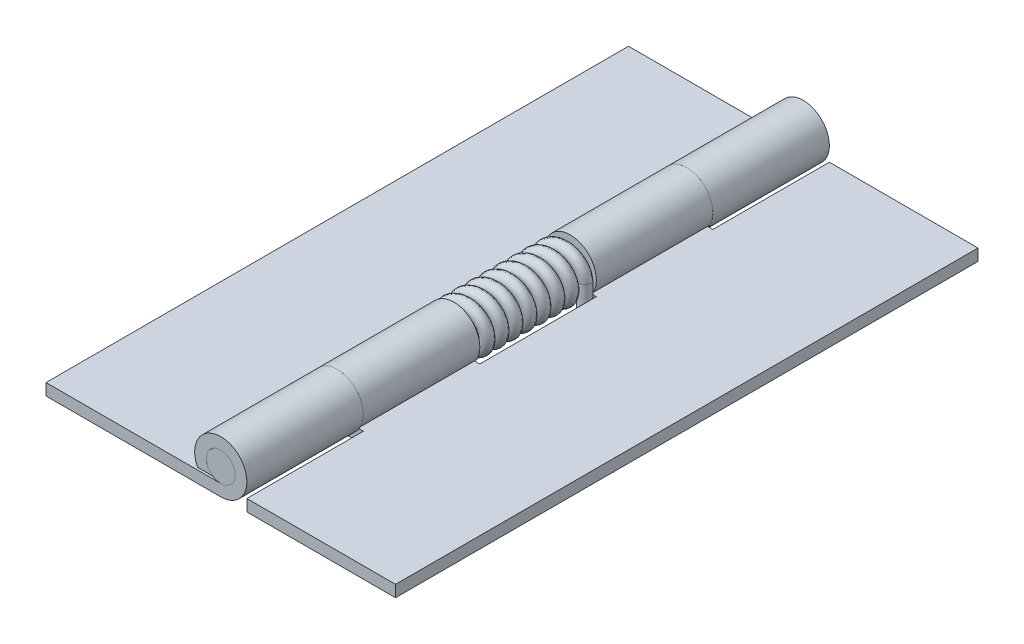
SolidWorks part; units mm, degrees
ref_plane "Front" through (0, 0, 0) normal (0, 0, 1) x (1, 0, 0)
ref_plane "Top" through (0, 0, 0) normal (0, 1, 0) x (1, 0, 0)
ref_plane "Right" through (0, 0, 0) normal (1, 0, 0) x (0, 0, -1)
sketch "Sketch1" plane through (0, 0, 0) normal (0, 0, 1) x (1, 0, 0)
  line L0 (-9.525, 0) -> (0, 0)
  line L1 (-9.525, 0) -> (-9.525, 0.635)
  line L2 (-9.525, 0.635) -> (0, 0.635)
  line L3 (-9.525, 0) -> (9.525, 0) construction
  line L4 (-1.2598, 0.762) -> (-0.4288, 0.762)
  circle A0 centre (0, 1.4224) radius 1.4224 construction
  circle A1 centre (0, 1.4224) radius 0.7874 construction
  arc A2 (0, 0.635) -> (-0.4288, 0.762) centre (0, 1.4224) ccw
  arc A3 (0, 0) -> (-1.2598, 0.762) centre (0, 1.4224) ccw
  dimension "D1" = 0.127
  dimension "Pin Dia" = 1.5748
  dimension "Thickness" = 0.635
  dimension "Open Wd" = 19.05
extrude "Extrude1" add sketch "Sketch1" against normal blind 31.75
sketch "Sketch2" plane through (0, 0, 0) normal (0, 1, 0) x (1, 0, 0)
  line L0 (1.4224, 0) -> (1.4224, 31.75) construction
  line L2 (-9.525, 0) -> (9.525, 0) construction
  line L5 (-1.4224, 31.75) -> (-1.4224, 0) construction
  line L6 (-1.4224, 25.4) -> (-1.4224, 31.75) construction
  line L11 (1.4224, 6.35) -> (-1.4224, 6.35)
  line L12 (1.4224, 6.35) -> (1.4224, 12.7)
  line L13 (1.4224, 12.7) -> (-1.4224, 12.7) construction
  line L14 (-1.4224, 6.35) -> (-1.4224, 12.7)
  line L16 (-1.4224, 6.35) -> (-1.4224, 0) construction
  line L17 (-1.4224, 12.7) -> (-1.4224, 19.05)
  line L19 (-1.4224, 19.05) -> (1.4224, 19.05) construction
  line L20 (-1.4224, 19.05) -> (-1.4224, 25.4)
  line L21 (-1.4224, 25.4) -> (1.4224, 25.4)
  line L22 (1.4224, 19.05) -> (1.4224, 25.4)
  line L23 (1.4224, 19.05) -> (1.4224, 12.7)
  dimension "D1" = 6.35
extrude "Cut-Extrude1" cut sketch "Sketch2" along normal through all
sketch "Sketch3" plane through (0, 0, 0) normal (0, 0, 1) x (1, 0, 0)
  line L0 (0, 0) -> (9.525, 0)
  line L1 (9.525, 0) -> (9.525, 0.635)
  line L2 (9.525, 0.635) -> (0, 0.635)
  line L3 (0.4288, 0.762) -> (1.2598, 0.762)
  line L4 (-1.2598, 0.762) -> (-0.4288, 0.762) construction
  arc A0 (0, 0) -> (1.2598, 0.762) centre (0, 1.4224) cw
  arc A1 (0, 0) -> (-1.2598, 0.762) centre (0, 1.4224) ccw construction
  arc A2 (0, 0.635) -> (0.4288, 0.762) centre (0, 1.4224) cw
  arc A3 (0, 0.635) -> (-0.4288, 0.762) centre (0, 1.4224) ccw construction
extrude "Extrude2" add sketch "Sketch3" against normal up to surface (31.75 mm away) separate body up to face at (-3.1558, 1.0886, -31.75)
sketch "Sketch4" plane through (0, 0, 0) normal (0, 1, 0) x (1, 0, 0)
  line L0 (-1.4224, 19.05) -> (-1.4224, 12.7)
  line L1 (-1.4224, 12.7) -> (1.4224, 12.7)
  line L2 (-1.4224, 0) -> (-1.4224, 6.35)
  line L3 (-1.4224, 6.35) -> (1.4224, 6.35)
  line L4 (1.4224, 6.35) -> (1.4224, 0)
  line L5 (1.4224, 0) -> (-1.4224, 0)
  line L7 (-1.4224, 19.05) -> (1.4224, 19.05)
  line L8 (1.4224, 12.7) -> (1.4224, 19.05)
  line L9 (-1.4224, 31.75) -> (1.4224, 31.75)
  line L10 (-1.4224, 31.75) -> (-1.4224, 25.4)
  line L11 (-1.4224, 25.4) -> (1.4224, 25.4)
  line L12 (1.4224, 31.75) -> (1.4224, 25.4)
extrude "Cut-Extrude2" cut sketch "Sketch4" along normal through all
sketch "Sketch5" plane through (0, 0, 0) normal (0, 0, 1) x (1, 0, 0)
  circle A0 centre (0, 1.4224) radius 0.7874
  arc A2 (0, 0.635) -> (-0.4288, 0.762) centre (0, 1.4224) ccw construction
extrude "Extrude3" add sketch "Sketch5" against normal up to surface (31.75 mm away) separate body up to face at (-3.1558, 1.0886, -31.75)
ref_plane "Plane4" through (0, 1.4224, 0) normal (0, 1, 0) x (-1, 0, 0)
sketch "Sketch15" plane through (0, 1.4224, 0) normal (0, 1, 0) x (0, 0, -1)
  line L0 (19.05, 1.4224) -> (19.05, -1.4224) construction
  line L2 (12.7, -1.4224) -> (12.7, 1.4224) construction
  line L3 (6.35, -1.4224) -> (12.7, -1.4224) construction
  line L4 (6.35, 1.4224) -> (12.7, 1.4224) construction
  circle A0 centre (18.7325, -1.1049) radius 0.3175
  circle A1 centre (13.0175, 1.1049) radius 0.3175
  dimension "D1" = 0.635
sketch "Sketch6" plane through (-38.1, 1.4224, -35.9283) normal (0, 1, 0) x (1, 0, 0)
  circle A0 centre (39.2049, -17.1958) radius 0.3175
  dimension "D1" = 0.635
ref_plane "Plane5" through (0, 0, -18.7325) normal (0, 0, 1) x (1, 0, 0)
sketch "Sketch9" plane through (0, 0, -18.7325) normal (0, 0, 1) x (1, 0, 0)
  line L2 (0, 1.4224) -> (1.1049, 1.4224) construction
  circle A0 centre (0, 1.4224) radius 1.1049
curve "Helix/Spiral2" pitch 0.762 height 5.715 radius 1.1049 centre (0, 1.4224, -18.7325) axis (0, 0, 1) start towards (1, 0, 0)
sketch "Sketch10" plane through (0, 0, -18.7325) normal (0, 0, 1) x (1, 0, 0)
  line L1 (1.5018, -0.3175) -> (8.3344, -0.3175)
  line L2 (1.4224, 0) -> (9.525, 0) construction
  line L3 (1.1049, 1.4224) -> (1.1049, 0.0794)
  line L5 (1.4224, 1.4224) -> (0.7874, 1.4224) construction
  arc A2 (1.1049, 0.0794) -> (1.5018, -0.3175) centre (1.5018, 0.0794) ccw
  dimension "D3" = 0.3969
  dimension "D1" = 0.3175
  dimension "D2" = 8.3344
sweep "Sweep12" add profiles "Sketch6" path "Helix/Spiral2"
sweep "Sweep5" add profiles "Sketch6<4>" path "Sketch10"
sketch "Sketch6<4>" plane through (-38.1, 1.4224, -35.9283) normal (0, 1, 0) x (1, 0, 0) same geometry as "Sketch6"
sketch "Sketch11" plane through (0, 1.4224, 0) normal (0, -1, 0) x (1, 0, 0)
  circle A0 centre (-1.1049, -13.0175) radius 0.3175
  circle A1 centre (1.1049, -18.7325) radius 0.3175 construction
ref_plane "Plane6" through (0, 0, -13.0175) normal (0, 0, 1) x (1, 0, 0)
sketch "Sketch12" plane through (0, 0, -13.0175) normal (0, 0, 1) x (1, 0, 0)
  line L3 (-1.1049, 1.4224) -> (-1.1049, 0.0794)
  line L4 (-0.7874, 1.4224) -> (-1.4224, 1.4224) construction
  line L5 (-1.5018, -0.3175) -> (-8.3344, -0.3175)
  line L6 (1.5018, -0.3175) -> (8.3344, -0.3175) construction
  arc A1 (-1.1049, 0.0794) -> (-1.5018, -0.3175) centre (-1.5018, 0.0794) cw
  arc A3 (1.1049, 0.0794) -> (1.5018, -0.3175) centre (1.5018, 0.0794) ccw construction
sweep "Sweep7" add profiles "Sketch11" path "Sketch12"
combine bodies "Combine1" operation type add bodies to combine 140 141 145
equation "\"D1@Sketch6\" = \"Thickness@Sketch1\""
equation "\"D1@Sketch10\" = \"Thickness@Sketch1\"/2"
equation "\"D2@Sketch10\" = (\"Open Wd@Sketch1\"/2)*.875"
equation "\"D3@Helix/Spiral2\" = \"D1@Sketch2\"-\"Thickness@Sketch1\""
equation "\"D1@Sketch15\" = \"Thickness@Sketch1\""
